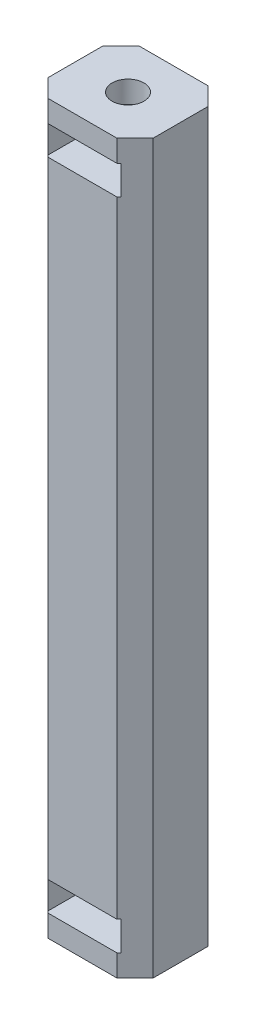
SolidWorks part; units mm, degrees
ref_plane "Front" through (0, 0, 0) normal (0, 0, 1) x (1, 0, 0)
ref_plane "Top" through (0, 0, 0) normal (0, 1, 0) x (1, 0, 0)
ref_plane "Right" through (0, 0, 0) normal (1, 0, 0) x (0, 0, -1)
sketch "草图1" plane through (0, 0, 0) normal (0, 1, 0) x (1, 0, 0)
  line L0 (-6.3312, 0) -> (6.528, 0) construction
  line L1 (-2.8868, 2.5) -> (-2.8868, -2.5)
  line L2 (2.8868, 2.5) -> (2.8868, -2.5)
  line L3 (2.8868, 2.5) -> (-2.8868, 2.5)
  line L6 (-2.8868, -2.5) -> (2.8868, -2.5)
  line L8 (-1.4434, 2.5) -> (-2.8868, 0) [skipped]
  line L9 (2.8868, 0) -> (1.4434, 2.5) [skipped]
  line L10 (-2.8868, 0) -> (-1.4434, -2.5) [skipped]
  line L11 (1.4434, -2.5) -> (2.8868, 0) [skipped]
  circle A0 centre (0, 0) radius 2.5 construction
  dimension "D1" = 5
extrude "凸台-拉伸1" add sketch "草图1" along normal blind 40
sketch "草图3" plane through (0, 40, 0) normal (0, 1, 0) x (1, 0, 0)
  point P0 (0, 0)
hole_wizard "M2.2x0.45 螺纹孔1" positions "3D草图2" profile "草图4" tap size "M2.2x0.45" standard "ANSI Metric" end condition through all
sketch3d "3D草图2"
  point P0 (0, 0, 0)
  point P3 (0, 0, 0)
  point P5 (0, 0, 0)
  point P7 (0, 40, 0)
sketch "草图4" plane through (0, 40, 0) normal (1, 0, 0) x (0, 0, 1)
  line L0 (0, 0) -> (0, 40)
  line L1 (0, 40) -> (0.875, 40)
  line L2 (0.875, 40) -> (0.875, 0)
  line L5 (0.875, 0) -> (0, 0)
  line L11 (0, -6.35) -> (0, 107.95) construction
  dimension "通孔螺纹孔钻头直径" = 1.75
  dimension "通孔螺纹孔钻头深度" = 40
cosmetic thread "孔螺蚊线1" parameters "D1"=40, "D2"=2.2
cosmetic thread "孔螺蚊线2" parameters "D1"=40, "D2"=2.2
cosmetic thread "孔螺蚊线3" parameters "D1"=40, "D2"=2.2
cosmetic thread "孔螺蚊线4" parameters "D1"=40, "D2"=2.2
ref_plane "基准面1" through (0, 2, 0) normal (0, -1, 0) x (-1, 0, 0)
ref_plane "基准面2" through (0, 38, 0) normal (0, 1, 0) x (1, 0, 0)
sketch "草图5" plane through (0, 2, 0) normal (0, -1, 0) x (-1, 0, 0)
  line L0 (-2, -1.1547) -> (-2, -2.5)
  line L1 (0, 2.3094) -> (-2, 1.1547)
  line L2 (-2, 1.1547) -> (-2, -1.1547)
  line L5 (2, -1.1547) -> (2, 1.1547)
  line L6 (2, 1.1547) -> (0, 2.3094)
  line L7 (2.8868, -2.5) -> (-2.8868, -2.5) construction
  line L8 (-2, -2.5) -> (2, -2.5)
  line L9 (2, -2.5) -> (2, -1.1547)
  line L11 (0, -2.3094) -> (2, -1.1547) [skipped]
  line L12 (-2, -1.1547) -> (0, -2.3094) [skipped]
  circle A0 centre (0, 0) radius 2 construction
extrude "切除-拉伸1" cut sketch "草图5" against normal mid plane 1.6
sketch "草图6" plane through (0, 38, 0) normal (0, 1, 0) x (1, 0, 0)
  line L7 (2, -2.5) -> (2, -1.1547)
  line L8 (-2, -2.5) -> (2, -2.5)
  line L9 (-2, -1.1547) -> (-2, -2.5)
  line L10 (-2, 1.1547) -> (-2, -1.1547)
  line L11 (0, 2.3094) -> (-2, 1.1547)
  line L12 (2, 1.1547) -> (0, 2.3094)
  line L13 (2, -1.1547) -> (2, 1.1547)
  line L14 (2, -2.5) -> (2, -1.1547)
  line L15 (-2, -2.5) -> (2, -2.5)
  line L16 (-2, -1.1547) -> (-2, -2.5)
  line L17 (-2, 1.1547) -> (-2, -1.1547)
  line L18 (0, 2.3094) -> (-2, 1.1547)
  line L19 (2, 1.1547) -> (0, 2.3094)
  line L20 (2, -1.1547) -> (2, 1.1547)
  dimension "D1" = 0
extrude "切除-拉伸2" cut sketch "草图6" against normal mid plane 1.6
chamfer "倒角1" distance 1 angle 45 4 edges at (-2.8868, 20, 2.5) (-2.8868, 20, -2.5) (2.8868, 20, -2.5) (2.8868, 20, 2.5)
